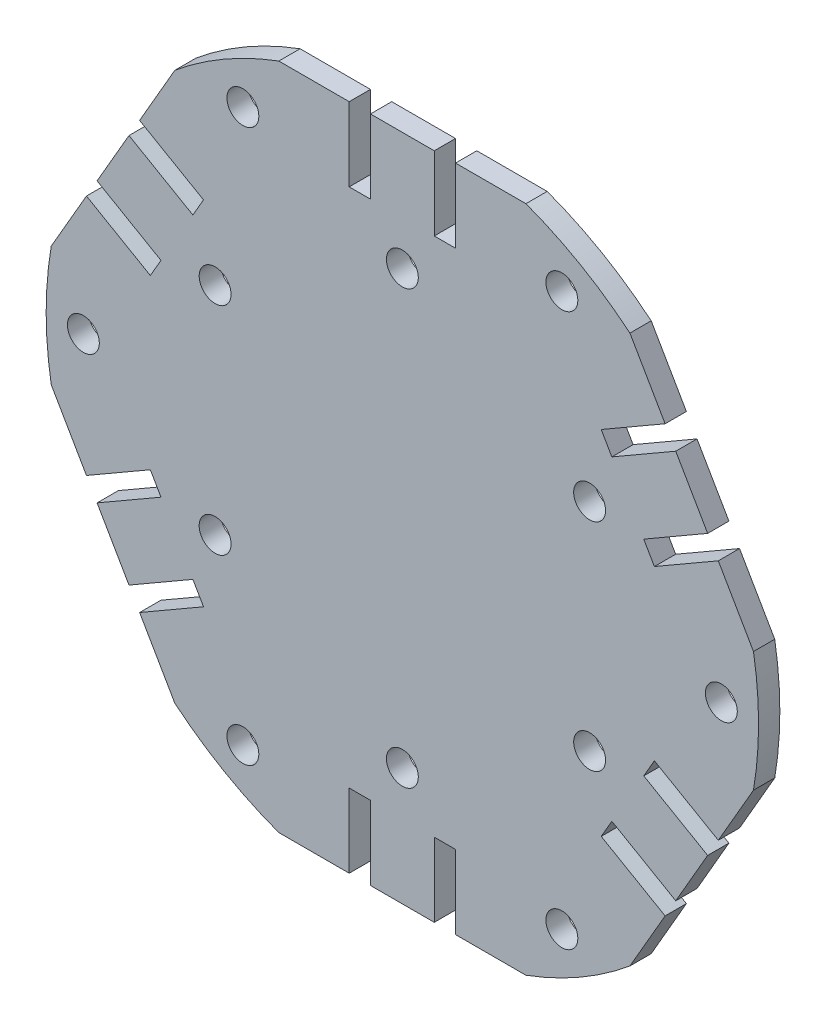
SolidWorks part; units mm, degrees
material "Acrylic (Medium-high impact)"
ref_plane "Front Plane" through (0, 0, 0) normal (0, 0, 1) x (1, 0, 0)
ref_plane "Top Plane" through (0, 0, 0) normal (0, 1, 0) x (1, 0, 0)
ref_plane "Right Plane" through (0, 0, 0) normal (1, 0, 0) x (0, 0, -1)
sketch "Model" plane through (0, 0, 0) normal (0, 0, 1) x (1, 0, 0)
  line L699 (-18.7014, -16.5708) -> (-19.7014, -14.8387)
  line L700 (-22.7014, -9.6426) -> (-23.7014, -7.9105)
  line L701 (-23.7014, -7.9105) -> (-29.7111, -11.3802)
  line L702 (-28.7111, -13.1122) -> (-22.7014, -9.6426)
  line L703 (-18.7014, -16.5708) -> (-24.7111, -20.0404)
  line L704 (-25.7111, -18.3084) -> (-19.7014, -14.8387)
  line L705 (-28.7111, -13.1122) -> (-25.7111, -18.3084)
  line L706 (-33.0204, -5.6482) -> (-29.7111, -11.3802)
  line L707 (-28.7111, -13.1122) -> (-25.7111, -18.3084)
  line L708 (-24.7111, -20.0404) -> (-21.4017, -25.7724)
  line L709 (-23.7014, 7.9105) -> (-22.7014, 9.6426)
  line L710 (-19.7014, 14.8387) -> (-18.7014, 16.5708)
  line L711 (-18.7014, 16.5708) -> (-24.7111, 20.0404)
  line L712 (-25.7111, 18.3084) -> (-19.7014, 14.8387)
  line L713 (-23.7014, 7.9105) -> (-29.7111, 11.3802)
  line L714 (-28.7111, 13.1122) -> (-22.7014, 9.6426)
  line L715 (-25.7111, 18.3084) -> (-28.7111, 13.1122)
  line L716 (-21.4017, 25.7724) -> (-24.7111, 20.0404)
  line L717 (-25.7111, 18.3084) -> (-28.7111, 13.1122)
  line L718 (-29.7111, 11.3802) -> (-33.0204, 5.6482)
  line L719 (5, -24.4813) -> (3, -24.4813)
  line L720 (-3, -24.4813) -> (-5, -24.4813)
  line L721 (-5, -24.4813) -> (-5, -31.4206)
  line L722 (-3, -31.4206) -> (-3, -24.4813)
  line L723 (5, -24.4813) -> (5, -31.4206)
  line L724 (3, -31.4206) -> (3, -24.4813)
  line L725 (-3, -31.4206) -> (3, -31.4206)
  line L726 (-11.6187, -31.4206) -> (-5, -31.4206)
  line L727 (-3, -31.4206) -> (3, -31.4206)
  line L728 (5, -31.4206) -> (11.6187, -31.4206)
  line L729 (23.7014, -7.9105) -> (22.7014, -9.6426)
  line L730 (19.7014, -14.8387) -> (18.7014, -16.5708)
  line L731 (18.7014, -16.5708) -> (24.7111, -20.0404)
  line L732 (25.7111, -18.3084) -> (19.7014, -14.8387)
  line L733 (23.7014, -7.9105) -> (29.7111, -11.3802)
  line L734 (28.7111, -13.1122) -> (22.7014, -9.6426)
  line L735 (25.7111, -18.3084) -> (28.7111, -13.1122)
  line L736 (21.4017, -25.7724) -> (24.7111, -20.0404)
  line L737 (25.7111, -18.3084) -> (28.7111, -13.1122)
  line L738 (29.7111, -11.3802) -> (33.0204, -5.6482)
  line L739 (-5, 24.4813) -> (-3, 24.4813)
  line L740 (3, 24.4813) -> (5, 24.4813)
  line L741 (5, 24.4813) -> (5, 31.4206)
  line L742 (3, 31.4206) -> (3, 24.4813)
  line L743 (-5, 24.4813) -> (-5, 31.4206)
  line L744 (-3, 31.4206) -> (-3, 24.4813)
  line L745 (3, 31.4206) -> (-3, 31.4206)
  line L746 (11.6187, 31.4206) -> (5, 31.4206)
  line L747 (3, 31.4206) -> (-3, 31.4206)
  line L748 (-5, 31.4206) -> (-11.6187, 31.4206)
  line L749 (23.7014, 7.9105) -> (22.7014, 9.6426)
  line L750 (19.7014, 14.8387) -> (18.7014, 16.5708)
  line L751 (18.7014, 16.5708) -> (24.7111, 20.0404)
  line L752 (25.7111, 18.3084) -> (19.7014, 14.8387)
  line L753 (23.7014, 7.9105) -> (29.7111, 11.3802)
  line L754 (28.7111, 13.1122) -> (22.7014, 9.6426)
  line L755 (25.7111, 18.3084) -> (28.7111, 13.1122)
  line L756 (21.4017, 25.7724) -> (24.7111, 20.0404)
  line L757 (25.7111, 18.3084) -> (28.7111, 13.1122)
  line L758 (29.7111, 11.3802) -> (33.0204, 5.6482)
  circle A324 centre (-17.6105, -10.1674) radius 1.5
  circle A325 centre (-17.6105, 10.1674) radius 1.5
  circle A326 centre (0, -20.3348) radius 1.5
  circle A327 centre (17.6105, -10.1674) radius 1.5
  circle A328 centre (0, 20.3348) radius 1.5
  arc A329 (33.0204, -5.6482) -> (33.0204, 5.6482) centre (0, 0) ccw
  arc A330 (21.4017, 25.7724) -> (11.6187, 31.4206) centre (0, 0) ccw
  arc A331 (-11.6187, 31.4206) -> (-21.4017, 25.7724) centre (0, 0) ccw
  arc A332 (-33.0204, 5.6482) -> (-33.0204, -5.6482) centre (0, 0) ccw
  arc A333 (-21.4017, -25.7724) -> (-11.6187, -31.4206) centre (0, 0) ccw
  arc A334 (11.6187, -31.4206) -> (21.4017, -25.7724) centre (0, 0) ccw
  circle A335 centre (-30, 0) radius 1.5
  circle A336 centre (-15, -25.9808) radius 1.5
  circle A337 centre (15, 25.9808) radius 1.5
  circle A338 centre (-15, 25.9808) radius 1.5
  circle A339 centre (15, -25.9808) radius 1.5
  circle A346 centre (30, 0) radius 1.5
  circle A349 centre (17.6105, 10.1674) radius 1.5
  dimension "D1" = 3
  dimension "D2" = 33.5
  dimension "D3" = 3
  dimension "D4" = 5
  dimension "D5" = 11.6187
  dimension "D6" = 15
  dimension "D7" = 17.6105
  dimension "D8" = 30
  dimension "D9" = 15
  dimension "D10" = 17.6105
  dimension "D11" = 18.7014
  dimension "D12" = 19.7014
  dimension "D13" = 30
  dimension "D14" = 10.1674
  dimension "D15" = 20.3348
  dimension "D16" = 25.9808
  dimension "D17" = 10.1674
  dimension "D18" = 20.3348
  dimension "D19" = 25.9808
extrude "Boss-Extrude1" add sketch "Model" along normal blind 2 contours L728 A334 L736 L731 L730 L732 L735 L734 L729 L733 L738 A329 L758 L753 L749 L754 L755 L752 L750 L751 L756 A330 L746 L741 L740 L742 L745 L744 L739 L743 L748 A331 L716 L711 L710 L712 L715 L714 L709 L713 L718 A332 L706 L701 L700 L702 L705 L704 L699 L703 L708 region at (0, 0, 0)
